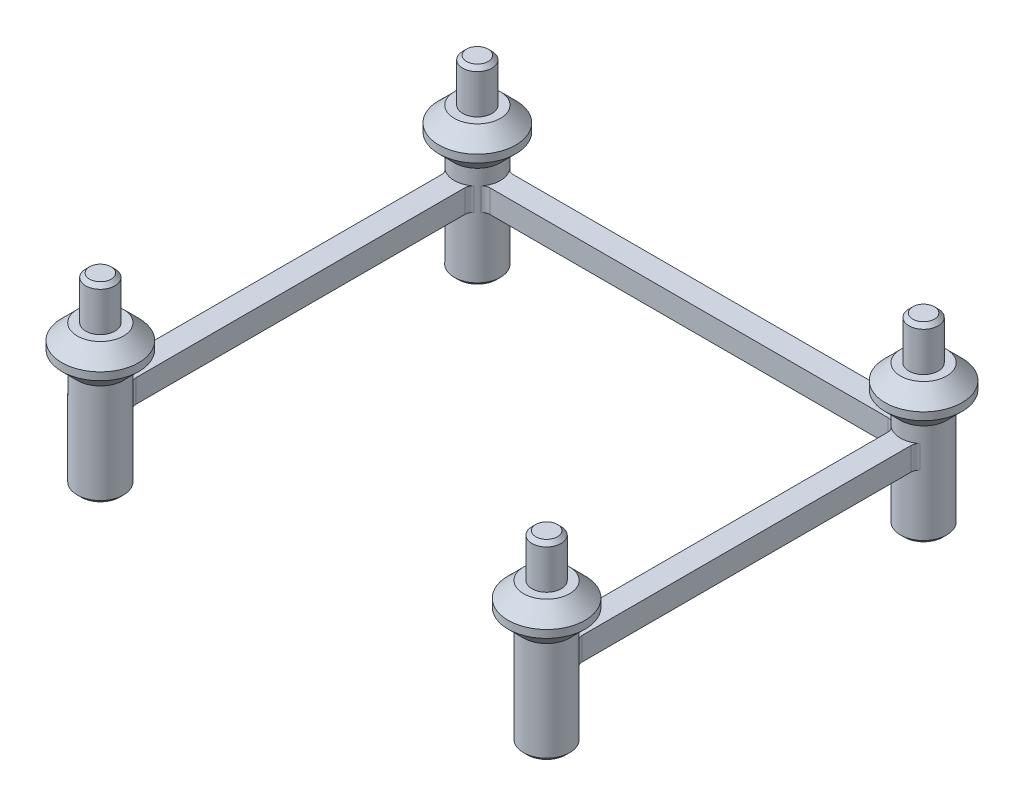
SolidWorks part; units mm, degrees
ref_plane "정면" through (0, 0, 0) normal (0, 0, 1) x (1, 0, 0)
ref_plane "윗면" through (0, 0, 0) normal (0, 1, 0) x (1, 0, 0)
ref_plane "우측면" through (0, 0, 0) normal (1, 0, 0) x (0, 0, -1)
sketch "스케치1" plane through (0, 0, 0) normal (0, 1, 0) x (1, 0, 0)
  line L0 (16.8257, 0) -> (-14.2029, 0) construction
  line L1 (0, -16.2693) -> (0, 25.1022) construction
  circle A0 centre (-29, 24.5) radius 3
  circle A1 centre (29, 24.5) radius 3
  circle A2 centre (-29, -24.5) radius 3
  circle A3 centre (29, -24.5) radius 3
  dimension "D3" = 6
  dimension "D1" = 58
  dimension "D2" = 49
extrude "보스-돌출1" add sketch "스케치1" along normal blind 18.4
sketch "스케치2" plane through (0, 0, 0) normal (0, -1, 0) x (1, 0, 0)
  circle A2 centre (-29, 24.5) radius 1.45
  circle A3 centre (-29, 24.5) radius 1.45
  circle A5 centre (29, 24.5) radius 1.45
  circle A6 centre (29, 24.5) radius 1.45
  circle A8 centre (-29, -24.5) radius 1.45
  circle A9 centre (-29, -24.5) radius 1.45
  circle A11 centre (29, -24.5) radius 1.45
  circle A12 centre (29, -24.5) radius 1.45
  dimension "D2" = 1.55
  dimension "D1" = 1.55
  dimension "D3" = 1.55
  dimension "D4" = 1.55
extrude "컷-돌출1" cut sketch "스케치2" against normal blind 5
sketch "스케치3" plane through (0, 18.4, 0) normal (0, 1, 0) x (1, 0, 0)
  circle A2 centre (29, 24.5) radius 5
  circle A3 centre (29, 24.5) radius 5
  circle A5 centre (29, -24.5) radius 5
  circle A6 centre (29, -24.5) radius 5
  circle A8 centre (-29, -24.5) radius 5
  circle A9 centre (-29, -24.5) radius 5
  circle A11 centre (-29, 24.5) radius 5
  circle A12 centre (-29, 24.5) radius 5
  dimension "D2" = 2
  dimension "D1" = 2
  dimension "D3" = 2
  dimension "D4" = 2
extrude "보스-돌출2" add sketch "스케치3" against normal blind 3
sketch "스케치4" plane through (0, 18.4, 0) normal (0, 1, 0) x (1, 0, 0)
  line L0 (29, 24.5) -> (29, -24.5) construction
  line L1 (29, -24.5) -> (27.5, -24.5) construction
  line L2 (-29, -24.5) -> (-29, 24.5) construction
  line L3 (-29, 24.5) -> (29, 24.5) construction
  line L4 (27.5, 23) -> (27.5, -23)
  line L6 (-27.5, -23) -> (-27.5, 23)
  line L7 (-27.5, 23) -> (27.5, 23)
  line L8 (30.5, 26) -> (30.5, -26)
  line L9 (30.5, -26) -> (27.5, -26)
  line L10 (-30.5, -26) -> (-30.5, 26)
  line L11 (-30.5, 26) -> (30.5, 26)
  line L12 (27.5, -23) -> (27.5, -26)
  line L13 (-27.5, -23) -> (-27.5, -26)
  line L14 (-27.5, -26) -> (-30.5, -26)
  line L15 (30.5, -26) -> (-30.5, -26) construction
  line L16 (-27.5, -24.5) -> (-29, -24.5) construction
  line L17 (29, -24.5) -> (-29, -24.5) construction
  line L19 (27.5, -23) -> (-27.5, -23) construction
  circle A1 centre (-29, 24.5) radius 5
  circle A2 centre (-29, 24.5) radius 5 construction
  circle A3 centre (-29, -24.5) radius 5
  arc A4 (-27.5, -19.7303) -> (-30.5, -19.7303) centre (-29, -24.5) ccw construction
  circle A5 centre (29, -24.5) radius 5
  circle A6 centre (29, -24.5) radius 5 construction
  circle A7 centre (29, 24.5) radius 5
  circle A8 centre (29, 24.5) radius 5 construction
  point P21 (0, 0)
  dimension "D1" = 0
  dimension "D2" = 0
  dimension "D3" = 0
  dimension "D4" = 0
  dimension "D5" = 1.5
  dimension "D6" = 1.5
extrude "보스-돌출3" add sketch "스케치4" against normal blind 3 from offset 7 offset against normal yes
chamfer "모따기1" distance 0.5 angle 45 8 edges at (29, 0, 27.5) (29, 0, 23.05) (29, 0, -27.5) (29, 0, -25.95) (-29, 0, 21.5) (-29, 0, 23.05) (-29, 0, -21.5) (-29, 0, -25.95)
sketch "스케치5" plane through (0, 18.4, 0) normal (0, 1, 0) x (1, 0, 0)
  circle A2 centre (29, 24.5) radius 1.9
  circle A3 centre (29, 24.5) radius 1.9
  circle A4 centre (29, -24.5) radius 1.9
  circle A5 centre (29, -24.5) radius 1.9
  circle A7 centre (-29, -24.5) radius 1.9
  circle A8 centre (-29, -24.5) radius 1.9
  circle A10 centre (-29, 24.5) radius 1.9
  circle A11 centre (-29, 24.5) radius 1.9
  dimension "D2" = 3.1
  dimension "D1" = 3.1
  dimension "D3" = 3.1
  dimension "D4" = 3.1
extrude "보스-돌출4" add sketch "스케치5" along normal blind 5.6
chamfer "모따기2" distance 0.5 angle 45 4 edges at (29, 24, 26.4) (-29, 24, 26.4) (-29, 24, -22.6) (29, 24, -22.6)
chamfer "모따기3" distance 2 angle 45 8 edges at (29, 18.4, 29.5) (29, 18.4, -19.5) (-29, 18.4, -19.5) (-29, 18.4, 29.5) (29, 15.4, -21.5) (29, 15.4, 27.5) (-29, 15.4, 27.5) (-29, 15.4, -21.5)
fillet "필렛1" radius 1 12 edges at (30.5, 9.9, -21.9019) (27.5, 9.9, -21.9019) (26.4019, 9.9, -23) (26.4019, 9.9, -26) (-26.4019, 9.9, -26) (-26.4019, 9.9, -23) (-27.5, 9.9, -21.9019) (-30.5, 9.9, -21.9019) (-30.5, 9.9, 21.9019) (30.5, 9.9, 21.9019) (27.5, 9.9, 21.9019) (-27.5, 9.9, 21.9019)
